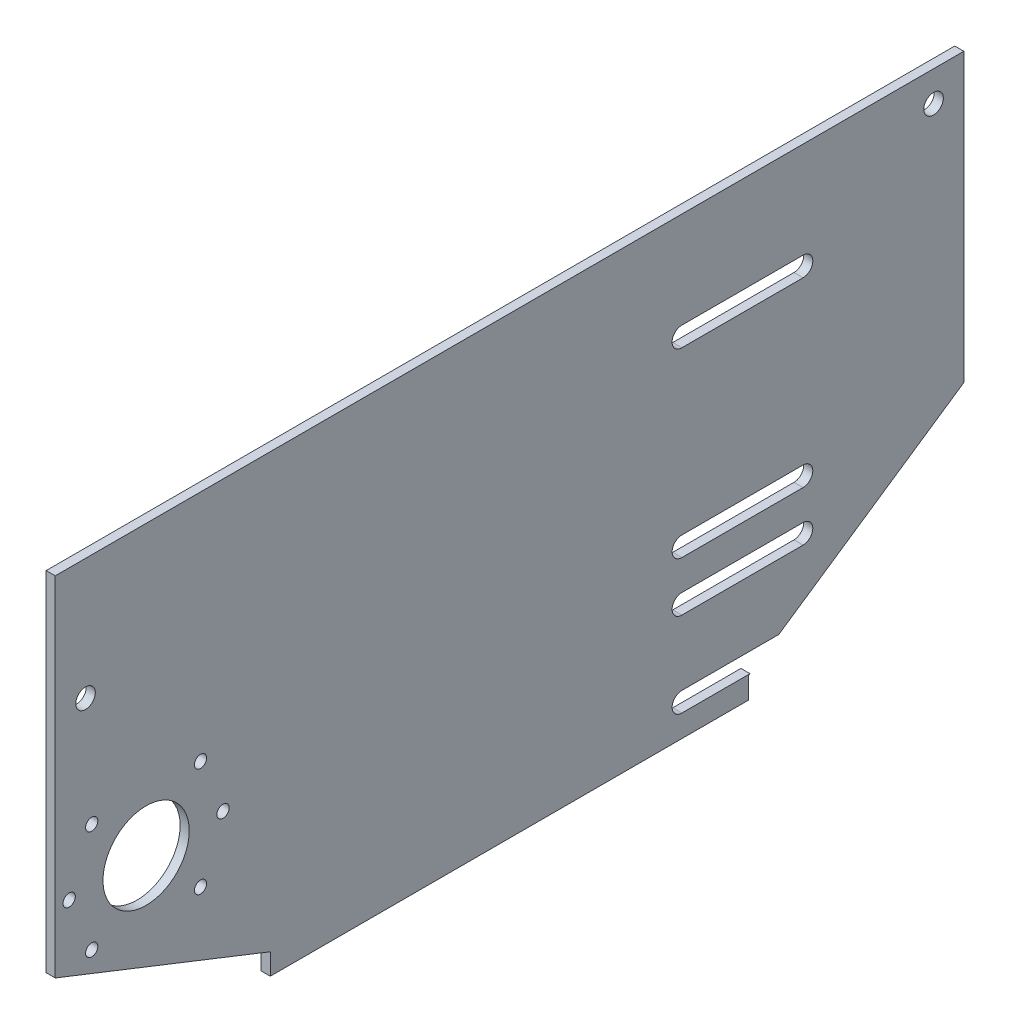
SolidWorks part; units mm, degrees
ref_plane "Front Plane" through (0, 0, 0) normal (0, 0, 1) x (1, 0, 0)
ref_plane "Top Plane" through (0, 0, 0) normal (0, 1, 0) x (1, 0, 0)
ref_plane "Right Plane" through (0, 0, 0) normal (1, 0, 0) x (0, 0, -1)
sketch "Sketch1" plane through (0, 0, 0) normal (1, 0, 0) x (0, 0, -1)
  line L1 (0, 0) -> (300, 0)
  line L2 (0, 0) -> (0, 150)
  line L3 (0, 150) -> (300, 150)
  line L4 (300, 0) -> (300, 150)
  circle A0 centre (30, 55) radius 14.235
  dimension "D1" = 300
  dimension "D5" = 28.47
  dimension "D4" = 55
  dimension "D2" = 150
  dimension "D3" = 30
extrude "Boss-Extrude1" add sketch "Sketch1" along normal blind 3
sketch "Sketch2" plane through (0, 0, 0) normal (-1, 0, 0) x (0, 0, 1)
  line L0 (-246.901, 55) -> (-206.901, 55) construction
  line L1 (-246.901, 58.225) -> (-206.901, 58.225)
  line L2 (-246.901, 51.775) -> (-206.901, 51.775)
  line L3 (-206.901, 115) -> (-246.901, 115) construction
  line L4 (-206.901, 111.77) -> (-246.901, 111.77)
  line L5 (-206.901, 118.23) -> (-246.901, 118.23)
  line L6 (-246.901, 38.55) -> (-206.901, 38.55) construction
  line L9 (-246.901, 41.775) -> (-206.901, 41.775)
  line L10 (-246.901, 35.325) -> (-206.901, 35.325)
  line L11 (-246.901, 10.55) -> (-206.901, 10.55) construction
  line L12 (-246.901, 13.775) -> (-206.901, 13.775)
  line L13 (-246.901, 7.325) -> (-206.901, 7.325)
  line L14 (0, 0) -> (-300, 0) construction
  line L15 (-300, 150) -> (0, 150) construction
  line L16 (-300, 0) -> (-300, 150) construction
  line L17 (0, 150) -> (0, 0) construction
  arc A0 (-246.901, 58.225) -> (-246.901, 51.775) centre (-246.901, 55) ccw
  arc A1 (-206.901, 51.775) -> (-206.901, 58.225) centre (-206.901, 55) ccw
  arc A3 (-206.901, 111.77) -> (-206.901, 118.23) centre (-206.901, 115) ccw
  arc A4 (-246.901, 118.23) -> (-246.901, 111.77) centre (-246.901, 115) ccw
  arc A7 (-246.901, 41.775) -> (-246.901, 35.325) centre (-246.901, 38.55) ccw
  arc A8 (-206.901, 35.325) -> (-206.901, 41.775) centre (-206.901, 38.55) ccw
  arc A9 (-246.901, 13.775) -> (-246.901, 7.325) centre (-246.901, 10.55) ccw
  arc A10 (-206.901, 7.325) -> (-206.901, 13.775) centre (-206.901, 10.55) ccw
  circle A11 centre (-290, 140) radius 3.225
  circle A12 centre (-10, 110) radius 3.225
  circle A13 centre (-290, 30) radius 3.225
  point P2 (-226.901, 55)
  point P9 (-226.901, 115)
  point P22 (-226.901, 38.55)
  point P34 (-226.901, 10.55)
  dimension "D1" = 3.225
  dimension "D4" = 3.225
  dimension "D6" = 40
  dimension "D8" = 3.225
  dimension "D13" = 6.45
  dimension "D14" = 6.45
  dimension "D15" = 6.45
  dimension "D3" = 40
  dimension "D5" = 40
  dimension "D7" = 10
  dimension "D9" = 40
  dimension "D10" = 60
  dimension "D11" = 28
  dimension "D12" = 55
  dimension "D16" = 10
  dimension "D17" = 10
  dimension "D18" = 30
  dimension "D19" = 10
  dimension "D20" = 10
  dimension "D21" = 110
extrude "Cut-Extrude1" cut sketch "Sketch2" against normal up to next
sketch "Sketch4" plane through (3, 0, 0) normal (1, 0, 0) x (0, 0, -1)
  line L4 (0, 150) -> (0, 0)
  line L5 (0, 0) -> (300, 0)
  line L6 (300, 0) -> (300, 150)
  line L7 (300, 150) -> (0, 150)
  line L8 (0, 150) -> (0, 0)
  line L9 (0, 0) -> (300, 0)
  line L10 (300, 0) -> (300, 150)
  line L11 (300, 150) -> (0, 150)
  circle A0 centre (47.9605, 37.0395) radius 2.0193 construction
  circle A1 centre (47.9605, 37.0395) radius 2.0193
  circle A2 centre (47.9605, 72.9605) radius 2.0193 construction
  circle A3 centre (47.9605, 72.9605) radius 2.0193
  circle A4 centre (55.4, 55) radius 2.0193 construction
  circle A5 centre (55.4, 55) radius 2.0193
  circle A6 centre (12.0395, 72.9605) radius 2.0193 construction
  circle A7 centre (12.0395, 72.9605) radius 2.0193
  circle A8 centre (4.6, 55) radius 2.0193 construction
  circle A9 centre (4.6, 55) radius 2.0193
  circle A10 centre (12.0395, 37.0395) radius 2.0193 construction
  circle A11 centre (12.0395, 37.0395) radius 2.0193
  dimension "D1" = 0
extrude "Cut-Extrude4" cut sketch "Sketch4" against normal through all contours A11 | A7 | A9 | A1 | A5 | A3 region at (3, 37.0395, -12.0395)
sketch "Sketch5" plane through (0, 0, 0) normal (-1, 0, 0) x (0, 0, 1)
  line L0 (-71, 7) -> (0, 35)
  line L1 (0, 150) -> (0, 0) construction
  line L2 (0, 35) -> (0, 0)
  line L3 (0, 0) -> (-71, 0)
  line L4 (-71, 7) -> (-71, 0) construction
  line L5 (0, 0) -> (-300, 0) construction
  line L6 (-71, 0) -> (-71, 7)
  dimension "D1" = 35
extrude "Cut-Extrude5" cut sketch "Sketch5" against normal through all
sketch "Sketch6" plane through (0, 0, 0) normal (-1, 0, 0) x (0, 0, 1)
  line L0 (-228.924, 7) -> (-300, 55.257)
  line L1 (-300, 0) -> (-300, 150) construction
  line L2 (-300, 55.257) -> (-300, 0)
  line L3 (-300, 0) -> (-228.924, 0)
  line L4 (-71, 0) -> (-300, 0) construction
  line L5 (-228.924, 7) -> (-228.924, 0) construction
  line L6 (-228.924, 0) -> (-228.924, 7)
  line L7 (-228.924, 7) -> (-228.924, 0)
  line M6 (-300, 150) -> (-300, 0)
  line M7 (-300, 0) -> (-71, 0)
  arc M14 (-246.901, 7.325) -> (-246.901, 13.775) centre (-246.901, 10.55) cw
  line M15 (-246.901, 13.775) -> (-206.901, 13.775)
  line M17 (-206.901, 7.325) -> (-246.901, 7.325)
  circle M18 centre (-290, 30) radius 3.225
extrude "Cut-Extrude6" cut sketch "Sketch6" against normal blind 10 contours L6 L0 M7 M17 M14 M15 M6 M18 region at (0, 18.9046, -274.9066)
